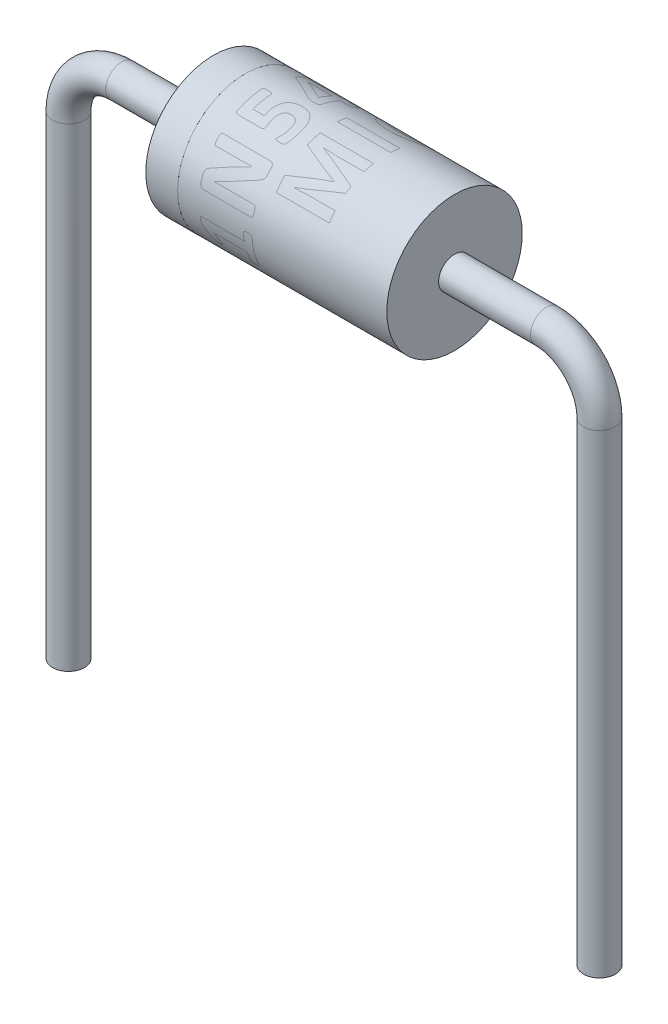
SolidWorks part; units mm, degrees
other "Diode"
other "Cathode Silver Band"
other "Wire"
ref_plane "Front Plane" through (0, 0, 0) normal (0, 0, 1) x (1, 0, 0)
ref_plane "Top Plane" through (0, 0, 0) normal (0, 1, 0) x (1, 0, 0)
ref_plane "Right Plane" through (0, 0, 0) normal (1, 0, 0) x (0, 0, -1)
sketch "Sketch1" plane through (0, 0, 0) normal (1, 0, 0) x (0, 0, -1)
  circle A0 centre (0, 0) radius 2.55
  circle A1 centre (0, 0) radius 0.6
  dimension "D1" = 5.1
  dimension "D2" = 1.2
extrude "Boss-Extrude1" add sketch "Sketch1" along normal mid plane 9.08
sketch "Sketch2" plane through (-4.54, 0, 0) normal (-1, 0, 0) x (0, 0, 1)
  circle A1 centre (0, 0) radius 2.55 construction
  circle A2 centre (0, 0) radius 2.54
  circle A3 centre (0, 0) radius 2.54
  circle A4 centre (0, 0) radius 2.55
  dimension "D1" = 0.01
extrude "Cut-Extrude1" cut sketch "Sketch2" against normal blind 1.2
sketch "Sketch3" plane through (-3.34, 0, 0) normal (-1, 0, 0) x (0, 0, 1)
  circle A0 centre (0, 0) radius 2.54 construction
  circle A1 centre (0, 0) radius 2.54
  circle A2 centre (0, 0) radius 2.55 construction
  circle A3 centre (0, 0) radius 2.55
extrude "Boss-Extrude2" add sketch "Sketch3" along normal up to surface (1.2 mm away) separate body up to face at (-4.54, 0, -0.6)
ref_plane "Plane1" through (0, 5, 0) normal (0, 1, 0) x (1, 0, 0)
sketch "Sketch4" plane through (0, 5, 0) normal (0, 1, 0) x (1, 0, 0)
  line L0 (-0.54, 7.5) -> (-0.54, -7.5) construction
  line L1 (-0.54, 0) -> (-4.54, 0) construction
  line L2 (-4.54, 2.55) -> (-4.54, -2.55) construction
  line L4 (-0.54, 0) -> (1.96, 0) construction
  line L5 (1.96, 7.5) -> (1.96, -7.5) construction
  text T0 "1N5400" font "Calibri" height 2
  text T1 "MIC" font "Corbel" height 2
  dimension "D1" = 4
  dimension "D2" = 15
  dimension "D3" = 2.5
wrap "Wrap1" sketch "Sketch4" wrap type scribe source sketch "Sketch4" face at (4.54, 0, -2.55)
sketch "Sketch5" plane through (0, 0, 0) normal (0, 0, 1) x (1, 0, 0)
  line L0 (0, 0) -> (-8, 0)
  line L1 (-10, -2) -> (-10, -19.8584)
  line L2 (0, 0) -> (8, 0)
  line L3 (10, -2) -> (10, -19.8584)
  arc A0 (-8, 0) -> (-10, -2) centre (-8, -2) ccw
  arc A1 (8, 0) -> (10, -2) centre (8, -2) cw
  dimension "D2" = 2
  dimension "D3" = 58
  dimension "D1" = 20
sketch "Sketch6" plane through (0, 0, 0) normal (1, 0, 0) x (0, 0, -1)
  circle A0 centre (0, 0) radius 0.6
  dimension "D1" = 1.2
sweep "Sweep1" add profiles "Sketch6" path "Sketch5"
